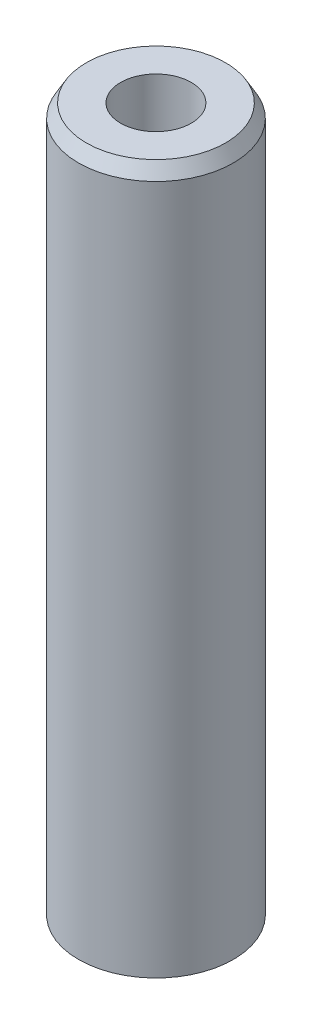
SolidWorks part; units mm, degrees
ref_plane "Front Plane" through (0, 0, 0) normal (0, 0, 1) x (1, 0, 0)
ref_plane "Top Plane" through (0, 0, 0) normal (0, 1, 0) x (1, 0, 0)
ref_plane "Right Plane" through (0, 0, 0) normal (1, 0, 0) x (0, 0, -1)
sketch "Sketch1" plane through (0, 0, 0) normal (0, 1, 0) x (1, 0, 0)
  circle A0 centre (0, 0) radius 32.5
  dimension "SHAFT_OD" = 65
extrude "Boss-Extrude1" add sketch "Sketch1" along normal blind 298.6791
sketch "Sketch2" plane through (0, 0, 0) normal (0, 1, 0) x (1, 0, 0)
  circle A0 centre (0, 0) radius 14.853
  dimension "BORE_D" = 29.7059
extrude "Cut-Extrude1" cut sketch "Sketch2" along normal through all
chamfer "Chamfer1" distance 5.6602 angle 30 2 edges at (0, 298.6791, 32.5) (0, 0, 32.5) first distance on face at (0, 298.6791, 32.5) first distance on face at (0, 0, 14.853)
